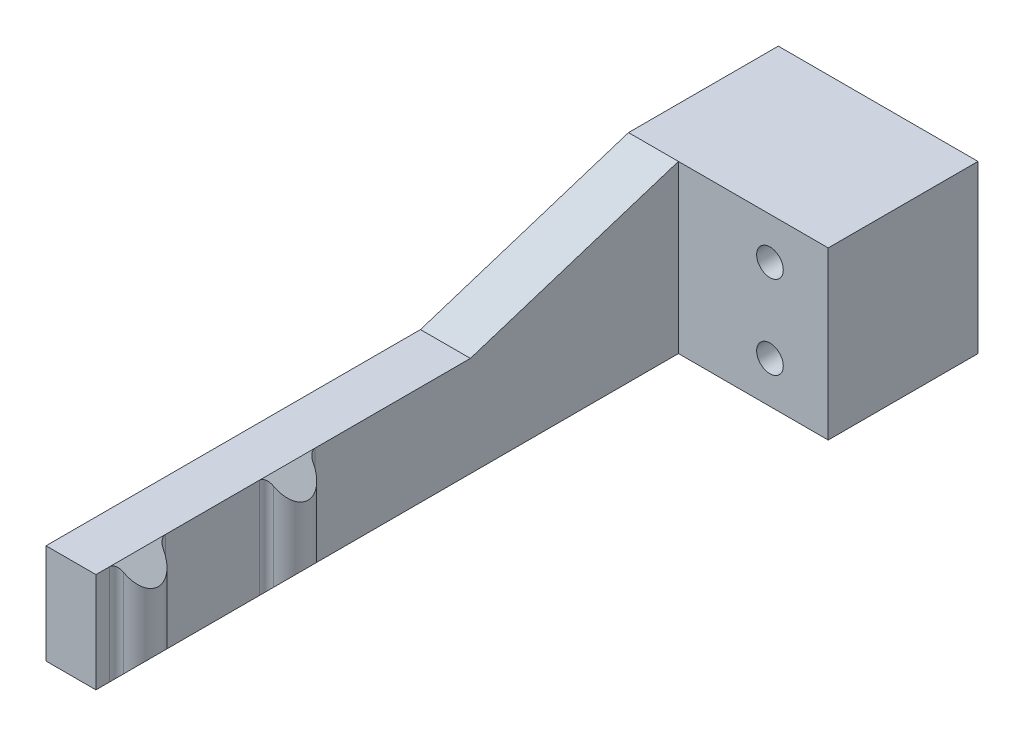
SolidWorks part; units mm, degrees
ref_plane "Front Plane" through (0, 0, 0) normal (0, 0, 1) x (1, 0, 0)
ref_plane "Top Plane" through (0, 0, 0) normal (0, 1, 0) x (1, 0, 0)
ref_plane "Right Plane" through (0, 0, 0) normal (1, 0, 0) x (0, 0, -1)
sketch "Sketch1" plane through (0, 0, 0) normal (0, 0, 1) x (1, 0, 0)
  line L1 (-12, -10) -> (12, -10)
  line L2 (-12, -10) -> (-12, 10)
  line L3 (-12, 10) -> (12, 10)
  line L4 (12, -10) -> (12, 10)
  line L5 (-12, -10) -> (12, 10) construction
  line L6 (-12, 10) -> (12, -10) construction
  point P0 (0, 0)
  dimension "D1" = 24
  dimension "D2" = 20
extrude "Boss-Extrude1" add sketch "Sketch1" along normal blind 18
sketch "Sketch2" plane through (0, 0, 18) normal (0, 0, 1) x (1, 0, 0)
  line L0 (12, 10) -> (-12, 10) construction
  line L2 (12, -10) -> (12, 10) construction
  circle A0 centre (5, 5) radius 1.6
  circle A1 centre (5, -5) radius 1.6
  point P8 (0, 0)
  dimension "D1" = 3.2
  dimension "D2" = 3.2
  dimension "D4" = 5
  dimension "D3" = 10
  dimension "D5" = 7
extrude "Cut-Extrude1" cut sketch "Sketch2" against normal through all
sketch "Sketch3" plane through (-12, 0, 0) normal (-1, 0, 0) x (0, 0, 1)
  line L0 (18, 10) -> (18, -10) construction
  line L1 (18, 2) -> (88, 2) construction
  line L2 (18, 2) -> (18, -10)
  line L3 (18, -10) -> (88, -10)
  line L4 (88, 2) -> (88, -10)
  line L5 (18, -10) -> (0, -10) construction
  line L6 (18, 10) -> (43, 2)
  line L7 (43, 2) -> (88, 2)
  line M7 (18, -10) -> (18, 10)
  dimension "D1" = 12
  dimension "D2" = 70
  dimension "D3" = 25
extrude "Boss-Extrude2" add sketch "Sketch3" against normal blind 6 contours L1 L3 L4 L7 M7 | L1 L6 M7 region at (-12, 4.6667, 26.3333) region at (-12, -4, 53)
ref_plane "Plane1" through (0, -7.5, 0) normal (0, -1, 0) x (-1, 0, 0)
sketch "Sketch4" plane through (0, -7.5, 0) normal (0, -1, 0) x (-1, 0, 0)
  line L0 (6, -43) -> (6, -88) construction
  line L1 (6, -88) -> (12, -88) construction
  line L2 (-12, -9) -> (-23.3005, -9) construction
  line L3 (-12, -18) -> (-12, 0) construction
  circle A0 centre (6, -83) radius 2.5
  circle A1 centre (6, -65) radius 2.5
  circle A2 centre (-40.6396, -74) radius 45 construction
  dimension "D1" = 5
  dimension "D3" = 5
  dimension "D4" = 90
  dimension "D2" = 5
  dimension "D5" = 65
extrude "Boss-Extrude3" add sketch "Sketch4" against normal blind 7
fillet "Fillet1" radius 1 4 edges at (-6, -4, 85.5) (-6, -4, 67.5) (-6, -4, 62.5) (-6, -4, 80.5)
chamfer "Chamfer2" distance 2.5 angle 45 4 edges at (-6, -0.5, 83) (-6, -0.5, 65) (-6, -7.5, 65) (-6, -7.5, 83)
